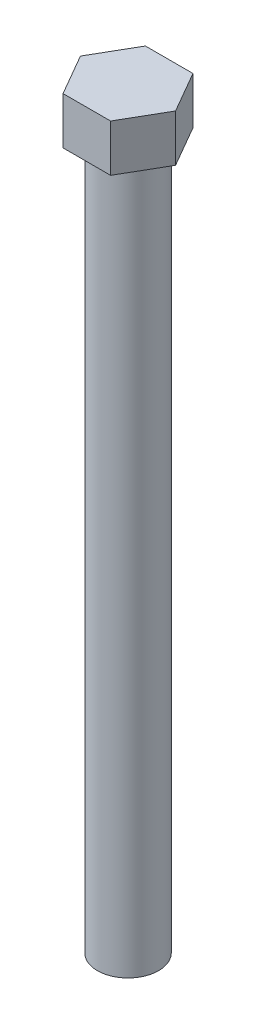
SolidWorks part; units mm, degrees
ref_plane "Front Plane" through (0, 0, 0) normal (0, 0, 1) x (1, 0, 0)
ref_plane "Top Plane" through (0, 0, 0) normal (0, 1, 0) x (1, 0, 0)
ref_plane "Right Plane" through (0, 0, 0) normal (1, 0, 0) x (0, 0, -1)
sketch "Sketch1" plane through (0, 0, 0) normal (0, 1, 0) x (1, 0, 0)
  line L1 (0.101, -0.175) -> (0.2021, 0)
  line L2 (0.2021, 0) -> (0.101, 0.175)
  line L3 (0.101, 0.175) -> (-0.101, 0.175)
  line L4 (-0.101, 0.175) -> (-0.2021, 0)
  line L5 (-0.2021, 0) -> (-0.101, -0.175)
  line L6 (-0.101, -0.175) -> (0.101, -0.175)
  circle A0 centre (0, 0) radius 0.175 construction
  circle A1 centre (0, 0) radius 0.13
  dimension "D2" = 0.26
  dimension "D1" = 0.35
extrude "Boss-Extrude1" add sketch "Sketch1" against normal blind 3 contours A1 region at (0, 0, 0)
extrude "Boss-Extrude2" add sketch "Sketch1<3>" along normal blind 0.2 contours L5 L6 L1 L2 L3 L4 A1 | A1 region at (0, 0, 0.1697) region at (0, 0, 0)
sketch "Sketch1<3>" plane through (0, 0, 0) normal (0, 1, 0) x (1, 0, 0) same geometry as "Sketch1"
